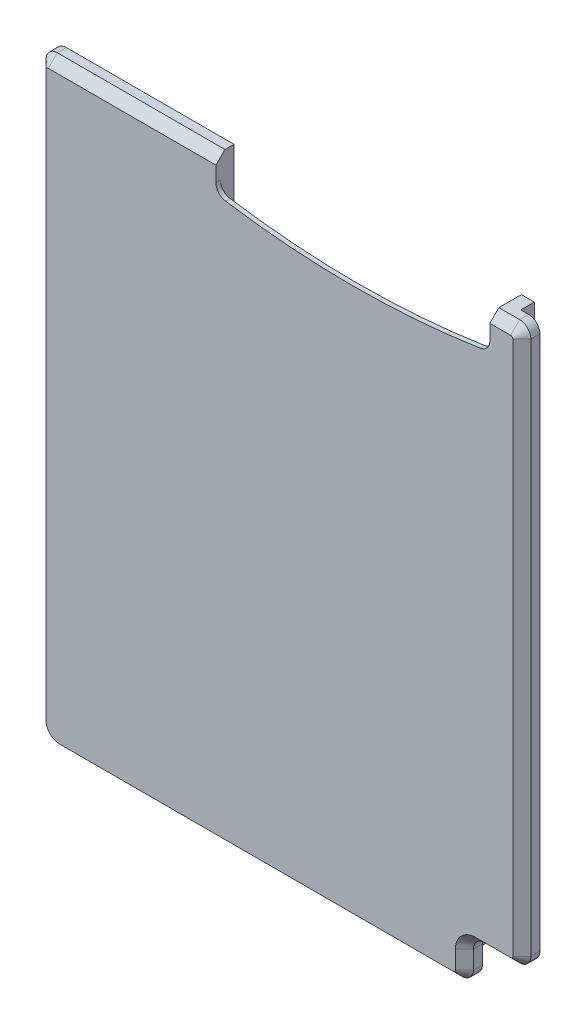
SolidWorks part; units mm, degrees
ref_plane "Ebene vorne" through (0, 0, 0) normal (0, 0, 1) x (1, 0, 0)
ref_plane "Ebene oben" through (0, 0, 0) normal (0, 1, 0) x (1, 0, 0)
ref_plane "Ebene rechts" through (0, 0, 0) normal (1, 0, 0) x (0, 0, -1)
ref_plane "Ebene1" through (0, 0, 1.2) normal (0, 0, 1) x (1, 0, 0)
ref_plane "Ebene2" through (12, 0, 0) normal (1, 0, 0) x (0, 0, -1)
sketch "Skizze2" plane through (0, 0, 1.2) normal (0, 0, 1) x (1, 0, 0)
  line L1 (1.25, 5.5) -> (22.75, 5.5)
  line L2 (1.25, 5.5) -> (1.25, 32)
  line L3 (1.25, 32) -> (22.75, 32)
  line L4 (22.75, 5.5) -> (22.75, 32)
  line L5 (12, -26.809) -> (12, 26.809) construction
  point P6 (12, 32)
  dimension "D1" = 21.5
  dimension "D2" = 5.5
  dimension "D3" = 32
extrude "Aufsatz-Linear austragen1" add sketch "Skizze2" along normal blind 0.8
sketch "Skizze3" plane through (0, 0, 1.2) normal (0, 0, 1) x (1, 0, 0)
  line L0 (21.9, 32) -> (21.9, 16.15)
  line L1 (22.75, 32) -> (1.25, 32) construction
  line L2 (21.9, 16.15) -> (19.9, 16.15)
  line L3 (19.9, 16.15) -> (19.9, 6.15)
  line L4 (19.9, 6.15) -> (2.1, 6.15)
  line L5 (2.1, 6.15) -> (2.1, 25.65)
  line L6 (2.1, 25.65) -> (10, 25.65)
  line L7 (10, 25.65) -> (10, 32)
  line L8 (10, 32) -> (21.9, 32)
  dimension "D1" = 21.9
  dimension "D2" = 10
  dimension "D3" = 2.1
  dimension "D4" = 19.9
  dimension "D5" = 16.15
  dimension "D6" = 6.15
  dimension "D7" = 25.65
extrude "Aufsatz-Linear austragen2" add sketch "Skizze3" against normal blind 0.6
sketch "Skizze5" plane through (0, 0, 1.2) normal (0, 0, 1) x (1, 0, 0)
  line L1 (21.3274, 16.4704) -> (9.1824, 16.4704)
  line L2 (21.3274, 16.4704) -> (21.3274, 25.0844)
  line L3 (21.3274, 25.0844) -> (9.1824, 25.0844)
  line L4 (9.1824, 16.4704) -> (9.1824, 25.0844)
extrude "Schnitt-Linear austragen2" cut sketch "Skizze5" against normal through all and the other way blind 0.7
sketch "Skizze4" plane through (0, 0, 1.2) normal (0, 0, 1) x (1, 0, 0)
  line L2 (8.3824, 24.5117) -> (5.0157, 24.5117)
  line L3 (5.0157, 24.5117) -> (5.0157, 25.65)
  line L4 (10, 25.65) -> (2.1, 25.65) construction
  line L5 (5.0157, 25.65) -> (2.1, 25.65)
  line L6 (2.1, 25.65) -> (2.1, 24.1349)
  line L7 (2.1, 25.65) -> (2.1, 6.15) construction
  line L8 (2.1, 24.1349) -> (2.6, 24.1349)
  line L9 (2.6, 24.1349) -> (2.6, 6.15)
  line L10 (2.6, 6.15) -> (7.9027, 6.15)
  line L11 (7.9027, 6.15) -> (7.9027, 7.35)
  line L12 (7.9027, 7.35) -> (10.3522, 7.35)
  line L13 (10.3522, 7.35) -> (10.3522, 6.15)
  line L14 (2.1, 6.15) -> (19.9, 6.15) construction
  line L15 (10.3522, 6.15) -> (16.321, 6.15)
  line L16 (16.321, 6.15) -> (16.321, 6.65)
  line L17 (16.321, 6.65) -> (19.9, 6.65)
  line L18 (19.9, 6.65) -> (19.9, 10.6244)
  line L19 (19.9, 10.6244) -> (18.9228, 10.6244)
  line L20 (18.9228, 10.6244) -> (18.9228, 12.0945)
  line L21 (18.9228, 12.0945) -> (18.2633, 12.0945)
  line L22 (18.2633, 12.0945) -> (18.2633, 15.6704)
  line L25 (21.3274, 16.4704) -> (16.321, 16.4704)
  line L26 (8.3824, 17.555) -> (8.3824, 24.5117)
  line L27 (16.321, 16.4704) -> (16.321, 15.6704)
  line L28 (16.321, 15.6704) -> (5.294, 15.6704)
  line L29 (5.294, 15.6704) -> (5.294, 17.555)
  line L30 (5.294, 17.555) -> (8.3824, 17.555)
  line L31 (9.1824, 23.6735) -> (8.3824, 23.6735) construction
  line L32 (9.1824, 25.0844) -> (9.1824, 16.4704) construction
  line L33 (9.1824, 16.4704) -> (21.3274, 16.4704) construction
  line L34 (19.9, 6.15) -> (19.9, 16.15) construction
  line L36 (9.1824, 16.4704) -> (21.3274, 16.4704) construction
  line L37 (21.3274, 16.4704) -> (21.3274, 16.15)
  line L38 (19.9, 16.15) -> (21.9, 16.15) construction
  line L39 (21.3274, 16.15) -> (19.9, 16.15)
  line L40 (19.9, 16.15) -> (19.9, 15.6704)
  line L41 (19.9, 6.15) -> (19.9, 16.15) construction
  line L42 (19.9, 15.6704) -> (18.2633, 15.6704)
  dimension "D1" = 0.8
  dimension "D2" = 0.8
  dimension "D3" = 0.5
  dimension "D4" = 1.2
  dimension "D6" = 0.5
extrude "Schnitt-Linear austragen1" cut sketch "Skizze4" against normal through all and the other way blind 0.4
sketch "Skizze6" plane through (0, 0, 1.2) normal (0, 0, 1) x (1, 0, 0)
  line L0 (21.3274, 25.0844) -> (9.1824, 25.0844) construction
  line L1 (21.3274, 25.0844) -> (9.1824, 25.0844)
  line L2 (21.3274, 25.0844) -> (21.3274, 33.108)
  line L3 (21.3274, 33.108) -> (9.1824, 33.108)
  line L4 (9.1824, 25.0844) -> (9.1824, 33.108)
  line L5 (21.031, 24.762) -> (9.511, 24.762) construction
  line L6 (21.3274, 16.15) -> (21.3274, 25.0844) construction
extrude "Schnitt-Linear austragen3" cut sketch "Skizze6" against normal through all and the other way blind 0.6
fillet "Verrundung1" radius 0.5 4 edges at (21.9, 16.15, 0.9) (2.1, 25.65, 1.4) (2.1, 6.15, 0.9) (19.9, 6.15, 0.9)
sketch "Skizze7" plane through (0, 0, 1.2) normal (0, 0, 1) x (1, 0, 0)
  line L0 (15.2549, 67.1251) -> (15.2549, 30) construction
  line L1 (9.1824, 25.0844) -> (21.3274, 25.0844) construction
  line L2 (21.3274, 30.5) -> (21.3274, 32.7999)
  line L3 (21.3274, 16.15) -> (21.3274, 32) construction
  line L4 (21.3274, 32.7999) -> (9.1824, 32.7999)
  line L5 (9.1824, 32.7999) -> (9.1824, 30.5)
  line L6 (9.1824, 32) -> (9.1824, 25.65) construction
  arc A0 (9.1824, 30.5) -> (21.3274, 30.5) centre (15.2549, 67.1251) ccw
  point P7 (15.2549, 25.0844)
  dimension "D1" = 30
  dimension "D2" = 30.5
extrude "Schnitt-Linear austragen4" cut sketch "Skizze7" against normal through all both and the other way through all
fillet "Verrundung3" radius 0.5 2 edges at (21.3274, 30.5, 1.9) (9.1824, 30.5, 1.9)
sketch "Skizze8" plane through (0, 0, 1.2) normal (0, 0, 1) x (1, 0, 0)
  line L1 (7.7194, 12.3003) -> (2.2575, 12.3003)
  line L2 (7.7194, 12.3003) -> (7.7194, 11.1003)
  line L3 (7.7194, 11.1003) -> (2.2575, 11.1003)
  line L4 (2.2575, 12.3003) -> (2.2575, 11.1003)
  line L5 (16.7764, 12.8433) -> (15.9764, 12.8433)
  line L6 (16.7764, 12.8433) -> (16.7764, 8.6762)
  line L7 (16.7764, 8.6762) -> (15.9764, 8.6762)
  line L8 (15.9764, 12.8433) -> (15.9764, 8.6762)
  dimension "D1" = 0.8
  dimension "D2" = 1.2
extrude "Aufsatz-Linear austragen3" add sketch "Skizze8" against normal blind 0.6 and the other way up to next
sketch "Skizze9" plane through (0, 0, 1.2) normal (0, 0, 1) x (1, 0, 0)
  line L1 (20.2, 5.135) -> (23.155, 5.135)
  line L2 (20.2, 5.135) -> (20.2, 7.3)
  line L3 (20.2, 7.3) -> (23.155, 7.3)
  line L4 (23.155, 5.135) -> (23.155, 7.3)
  dimension "D1" = 7.3
  dimension "D2" = 20.2
extrude "Schnitt-Linear austragen5" cut sketch "Skizze9" against normal through all both and the other way through all
sketch "Skizze10" plane through (0, 0, 1.2) normal (0, 0, 1) x (1, 0, 0)
  line L1 (20.0372, 8.0841) -> (19.2668, 8.0841)
  line L2 (20.0372, 8.0841) -> (20.0372, 5.9134)
  line L3 (20.0372, 5.9134) -> (19.2668, 5.9134)
  line L4 (19.2668, 8.0841) -> (19.2668, 5.9134)
extrude "Aufsatz-Linear austragen4" add sketch "Skizze10" along normal blind 0.8
fillet "Verrundung2" radius 1 1 edges at (1.25, 5.5, 1.6)
fillet "Verrundung4" radius 0.5 5 edges at (22.75, 32, 1.6) (1.25, 32, 1.6) (22.75, 7.3, 1.6) (20.2, 7.3, 1.6) (20.2, 5.5, 1.6)
chamfer "Fase1" distance 0.4 angle 45 13 edges at (22.75, 19.65, 2) (1.25, 19, 2) (10.975, 5.5, 2) (1.5429, 5.7929, 2) (21.7887, 32, 2) (22.6036, 31.8536, 2) (5.4662, 32, 2) (1.3964, 31.8536, 2) (22.6036, 7.4464, 2) (21.475, 7.3, 2) (20.3464, 7.1536, 2) (20.2, 6.4, 2) (20.0536, 5.6464, 2)
